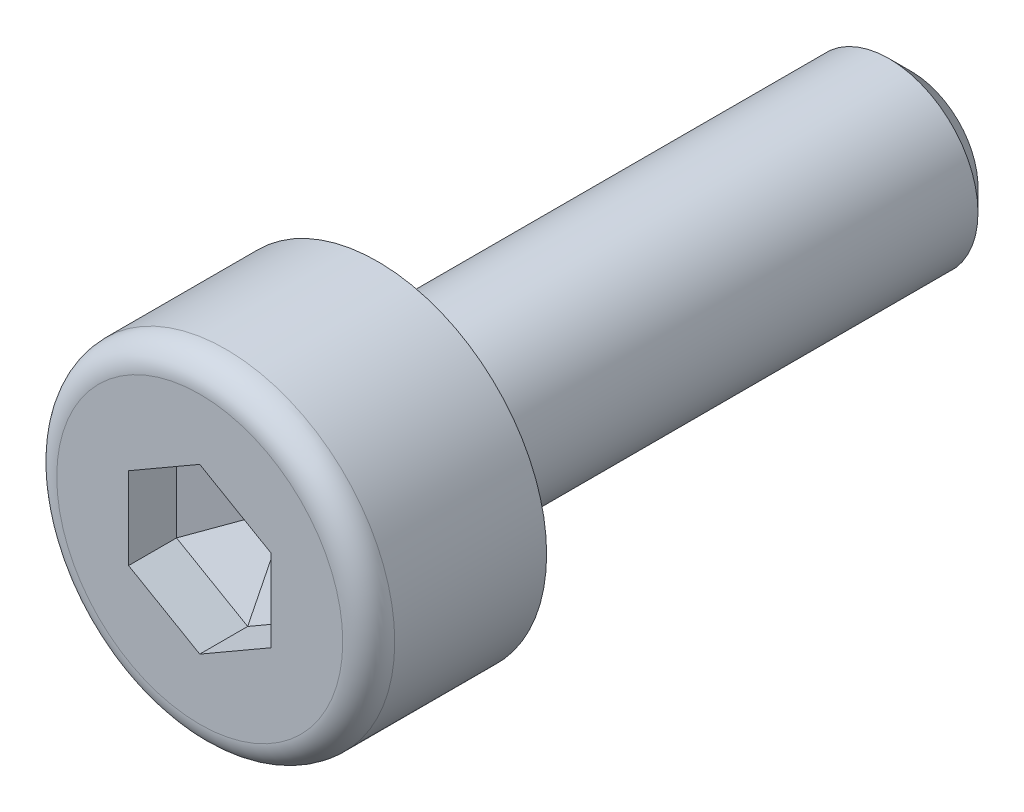
SolidWorks part; units mm, degrees
ref_plane "前视基准面" through (0, 0, 0) normal (0, 0, 1) x (1, 0, 0)
ref_plane "上视基准面" through (0, 0, 0) normal (0, 1, 0) x (1, 0, 0)
ref_plane "右视基准面" through (0, 0, 0) normal (1, 0, 0) x (0, 0, -1)
sketch "草图1" plane through (0, 0, 0) normal (0, 0, 1) x (1, 0, 0)
  circle A0 centre (0, 0) radius 1.9
  dimension "dk" = 3.8
extrude "凸台-拉伸1" add sketch "草图1" along normal blind 2
ref_axis "基准轴1" through (0, 0, 2) along (0, 0, -1)
sketch "草图2" plane through (0, 0, 2) normal (0, 0, 1) x (1, 0, 0)
  line L1 (0.8, 0.4619) -> (0, 0.9238)
  line L2 (0, 0.9238) -> (-0.8, 0.4619)
  line L3 (-0.8, 0.4619) -> (-0.8, -0.4619)
  line L4 (-0.8, -0.4619) -> (0, -0.9238)
  line L5 (0, -0.9238) -> (0.8, -0.4619)
  line L6 (0.8, -0.4619) -> (0.8, 0.4619)
  circle A0 centre (0, 0) radius 0.8 construction
  dimension "s" = 1.6
extrude "切除-拉伸1" cut sketch "草图2" against normal blind 1
sketch "草图3" plane through (0, 0, 0) normal (0, 0, -1) x (-1, 0, 0)
  circle A0 centre (0, 0) radius 1
  dimension "d" = 2
extrude "凸台-拉伸2" add sketch "草图3" along normal blind 6
cosmetic thread "装饰螺纹线1" parameters "b"=4.9, "D2"=1.221
chamfer "倒角1" distance 0.25 angle 45 1 edges at (-1, 0, -6)
fillet "圆角1" radius 0.2923 1 edges at (1.9, 0, 2)
chamfer "倒角2" distance 0.4611 angle 60 6 edges at (-0.8, 0, 1) (-0.4, 0.6928, 1) (0.4, 0.6928, 1) (0.8, 0, 1) (-0.4, -0.6928, 1) (0.4, -0.6928, 1) first distance on face at (-0.8, 0, 1.5) first distance on face at (-0.4, 0.6928, 1.5) first distance on face at (0.4, 0.6928, 1.5) first distance on face at (0.8, 0, 1.5) first distance on face at (-0.4, -0.6928, 1.5) first distance on face at (0.4, -0.6928, 1.5)
fillet "圆角2" radius 0.1 1 edges at (1, 0, 0)
ref_plane "基准面1" through (0, 0, 0) normal (0, 0, -1) x (-1, 0, 0)
equation "\"D1@倒角2\" = \"s@草图2\" / 3.47"
equation "\"D1@圆角1\"= \"dk@草图1\" / 13"
equation "\"D1@倒角1\"= \"d@草图3\" / 8"
equation "\"D1@圆角2\"= \"d@草图3\" / \"d@草图3\" * 0.1"
